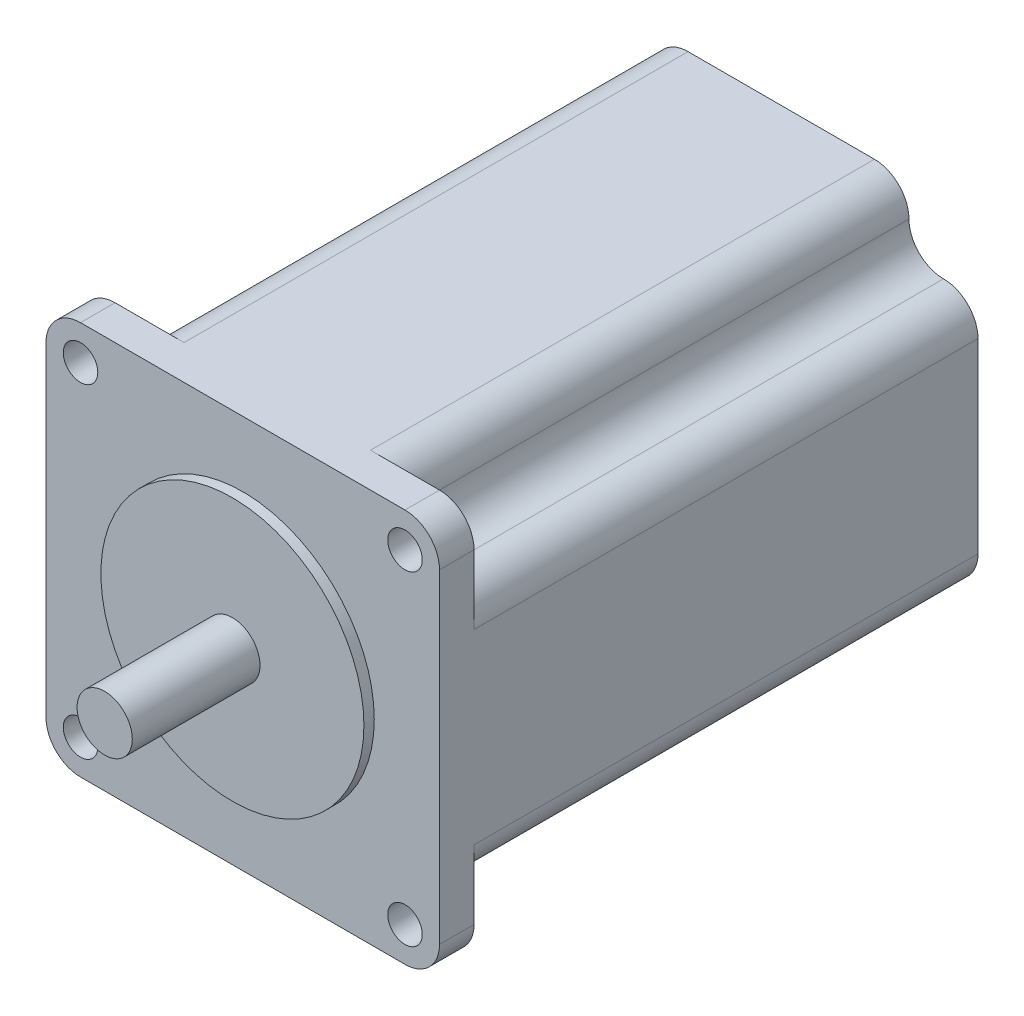
SolidWorks part; units mm, degrees
ref_plane "Front Plane" through (0, 0, 0) normal (0, 0, 1) x (1, 0, 0)
ref_plane "Top Plane" through (0, 0, 0) normal (0, 1, 0) x (1, 0, 0)
ref_plane "Right Plane" through (0, 0, 0) normal (1, 0, 0) x (0, 0, -1)
sketch "Sketch1" plane through (0, 0, 0) normal (0, 0, 1) x (1, 0, 0)
  line L1 (-33.3612, 31.2642) -> (23.6388, 31.2642)
  line L2 (-33.3612, 31.2642) -> (-33.3612, -25.7358)
  line L3 (-33.3612, -25.7358) -> (23.6388, -25.7358)
  line L4 (23.6388, 31.2642) -> (23.6388, -25.7358)
  dimension "D1" = 57
  dimension "D2" = 57
extrude "Boss-Extrude1" add sketch "Sketch1" along normal blind 78
sketch "Sketch2" plane through (0, 0, 0) normal (0, 0, -1) x (-1, 0, 0)
  line L1 (-23.6388, 31.2642) -> (-13.6388, 31.2642)
  line L2 (-23.6388, 31.2642) -> (-23.6388, 21.2642)
  line L3 (-23.6388, 21.2642) -> (-13.6388, 21.2642)
  line L4 (-13.6388, 31.2642) -> (-13.6388, 21.2642)
  dimension "D1" = 10
  dimension "D2" = 10
extrude "Cut-Extrude1" cut sketch "Sketch2" against normal blind 73
pattern_linear "LPattern1" count 2 spacing 47 along (-1, 0, 0) count 2 spacing 47 along (0, -1, 0) of "Cut-Extrude1"
sketch "Sketch3" plane through (0, 0, 78) normal (0, 0, 1) x (1, 0, 0)
  line L0 (23.6388, 31.2642) -> (-33.3612, 31.2642) construction
  line L1 (-33.3612, 31.2642) -> (-33.3612, -25.7358) construction
  circle A0 centre (-28.3612, 26.2642) radius 2.5
  dimension "D3" = 5
  dimension "D1" = 5
  dimension "D2" = 5
extrude "Cut-Extrude2" cut sketch "Sketch3" against normal blind 50
pattern_linear "LPattern2" count 2 spacing 47 along (1, 0, 0) count 2 spacing 47 along (0, -1, 0) of "Cut-Extrude2"
fillet "Fillet1" radius 5 16 edges at (-33.3612, 21.2642, 36.5) (-23.3612, 21.2642, 36.5) (-23.3612, 31.2642, 36.5) (13.6388, 31.2642, 36.5) (13.6388, 21.2642, 36.5) (23.6388, 21.2642, 36.5) (23.6388, -25.7358, 75.5) (23.6388, -15.7358, 36.5) (13.6388, -15.7358, 36.5) (13.6388, -25.7358, 36.5) (-23.3612, -25.7358, 36.5) (-23.3612, -15.7358, 36.5) (-33.3612, -15.7358, 36.5) (-33.3612, -25.7358, 75.5) (-33.3612, 31.2642, 75.5) (23.6388, 31.2642, 75.5)
sketch "Sketch5" plane through (0, 0, 78) normal (0, 0, 1) x (1, 0, 0)
  line L0 (18.6388, 31.2642) -> (-28.3612, 31.2642) construction
  line L1 (-33.3612, 26.2642) -> (-33.3612, -20.7358) construction
  circle A0 centre (-4.8612, 2.7642) radius 19.05
  dimension "D1" = 28.5
  dimension "D2" = 28.5
extrude "Boss-Extrude3" add sketch "Sketch5" along normal blind 1.5
sketch "Sketch4" plane through (0, 0, 78) normal (0, 0, 1) x (1, 0, 0)
  line L0 (18.6388, 31.2642) -> (-28.3612, 31.2642) construction
  line L1 (23.6388, -20.7358) -> (23.6388, 26.2642) construction
  circle A0 centre (-4.8612, 2.7642) radius 4
  dimension "D3" = 8
  dimension "D1" = 28.5
  dimension "D2" = 28.5
extrude "Boss-Extrude2" add sketch "Sketch4" along normal blind 20
